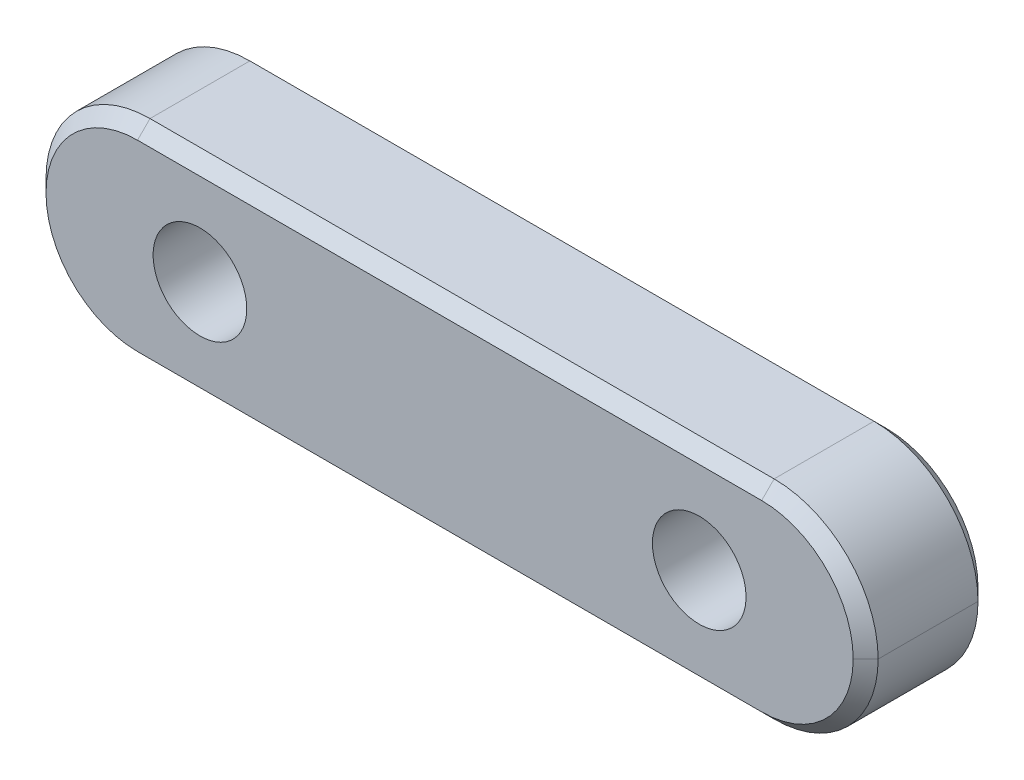
SolidWorks part; units mm, degrees
ref_plane "Front Plane" through (0, 0, 0) normal (0, 0, 1) x (1, 0, 0)
ref_plane "Top Plane" through (0, 0, 0) normal (0, 1, 0) x (1, 0, 0)
ref_plane "Right Plane" through (0, 0, 0) normal (1, 0, 0) x (0, 0, -1)
sketch "Sketch1" plane through (0, 0, 0) normal (0, 0, 1) x (1, 0, 0)
  line L1 (-20, -5) -> (20, -5)
  line L2 (-20, -5) -> (-20, 5)
  line L3 (-20, 5) -> (20, 5)
  line L4 (20, -5) -> (20, 5)
  line L5 (-20, -5) -> (20, 5) construction
  line L6 (-20, 5) -> (20, -5) construction
  point P0 (0, 0)
  dimension "D1" = 40
  dimension "D2" = 10
extrude "Boss-Extrude1" add sketch "Sketch1" along normal blind 6
sketch "Sketch2" plane through (0, 0, 6) normal (0, 0, 1) x (1, 0, 0)
  line L0 (0, 5) -> (0, -5) construction
  line L1 (20, 5) -> (-20, 5) construction
  line L2 (-20, -5) -> (20, -5) construction
  line L3 (20, 0) -> (-20, 0) construction
  line L4 (20, -5) -> (20, 5) construction
  line L5 (-20, 5) -> (-20, -5) construction
  circle A0 centre (-12, 0) radius 2.25
  circle A1 centre (12, 0) radius 2.25
  dimension "D1" = 4.5
  dimension "D2" = 12
extrude "Cut-Extrude1" cut sketch "Sketch2" against normal blind 6
fillet "Fillet1" radius 5 4 edges at (20, -5, 3) (20, 5, 3) (-20, -5, 3) (-20, 5, 3)
chamfer "Chamfer1" distance 0.6 angle 45 12 edges at (0, -5, 0) (18.5355, -3.5355, 0) (-18.5355, -3.5355, 0) (18.5355, 3.5355, 0) (-18.5355, 3.5355, 0) (0, 5, 0) (0, -5, 6) (18.5355, -3.5355, 6) (-18.5355, -3.5355, 6) (18.5355, 3.5355, 6) (-18.5355, 3.5355, 6) (0, 5, 6)
